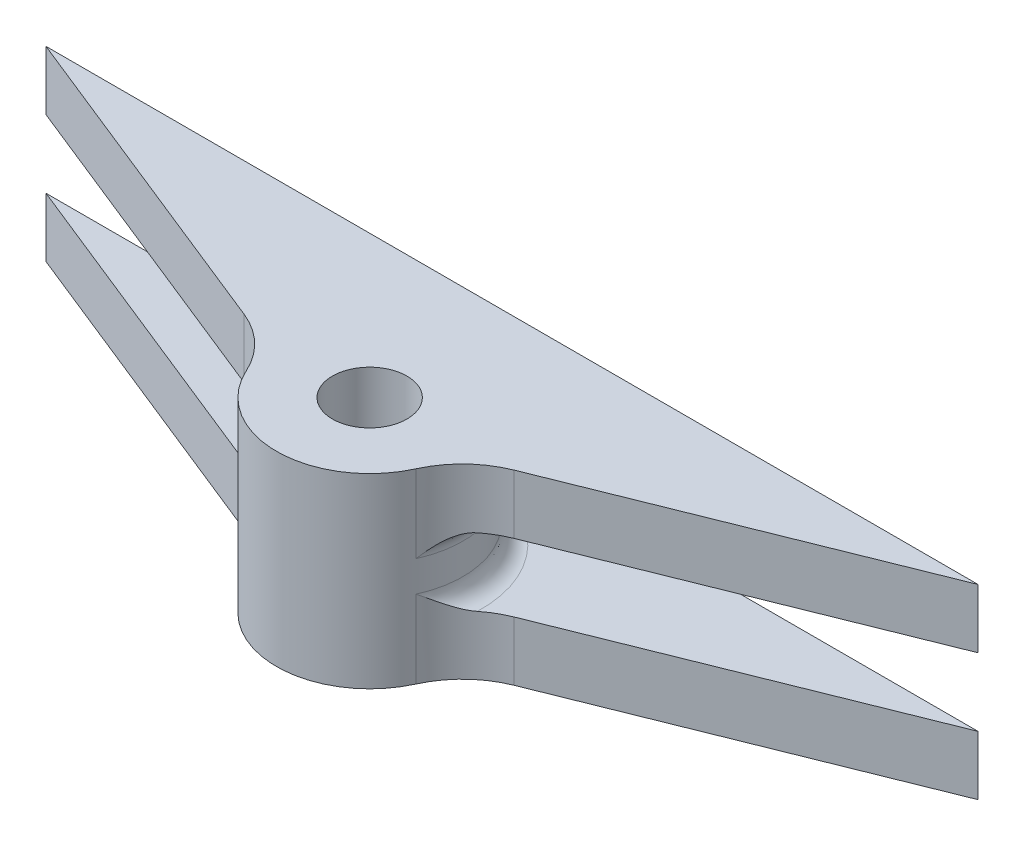
SolidWorks part; units mm, degrees
ref_plane "Front Plane" through (0, 0, 0) normal (0, 0, 1) x (1, 0, 0)
ref_plane "Top Plane" through (0, 0, 0) normal (0, 1, 0) x (1, 0, 0)
ref_plane "Right Plane" through (0, 0, 0) normal (1, 0, 0) x (0, 0, -1)
sketch "Sketch1" plane through (0, 0, 0) normal (0, 1, 0) x (1, 0, 0)
  line L0 (0, 0) -> (100, 0)
  line L4 (0, 0) -> (40.0326, -16.076)
  line L5 (59.9674, -16.076) -> (100, 0)
  line L6 (50, 0) -> (50, -17.1488) construction
  line L7 (40.0326, -16.076) -> (59.9674, -16.076) construction
  circle A0 centre (50, -15.2697) radius 4
  circle A1 centre (50, -15.2697) radius 10
  point P10 (0, 0)
  dimension "D2" = 20
  dimension "D3" = 8
  dimension "D1" = 100
extrude "Boss-Extrude1" add sketch "Sketch1" along normal blind 6.35 contours A1 L5 L0 L4 region at (50, 0, 5.1088)
extrude "Boss-Extrude2" add sketch "Sketch1<3>" along normal blind 20 contours A1 A0 region at (49.6079, 0, 5.5605)
sketch "Sketch1<3>" plane through (0, 0, 0) normal (0, 1, 0) x (1, 0, 0) same geometry as "Sketch1"
ref_plane "Plane1" through (0, 10, 0) normal (0, 1, 0) x (1, 0, 0)
mirror "Mirror1" about plane through (0, 10, 0) normal (0, 1, 0) of "Boss-Extrude1"
ref_plane "Plane2" through (59.9674, 13.65, 16.076) normal (0, 1, 0) x (1, 0, 0)
fillet "Fillet1" radius 10 4 edges at (59.9674, 3.175, 16.076) (40.0326, 3.175, 16.076) (40.0326, 16.825, 16.076) (59.9674, 16.825, 16.076)
fillet "Fillet2" radius 2 2 edges at (50, 6.35, 5.2697) (50, 13.65, 5.2697)
